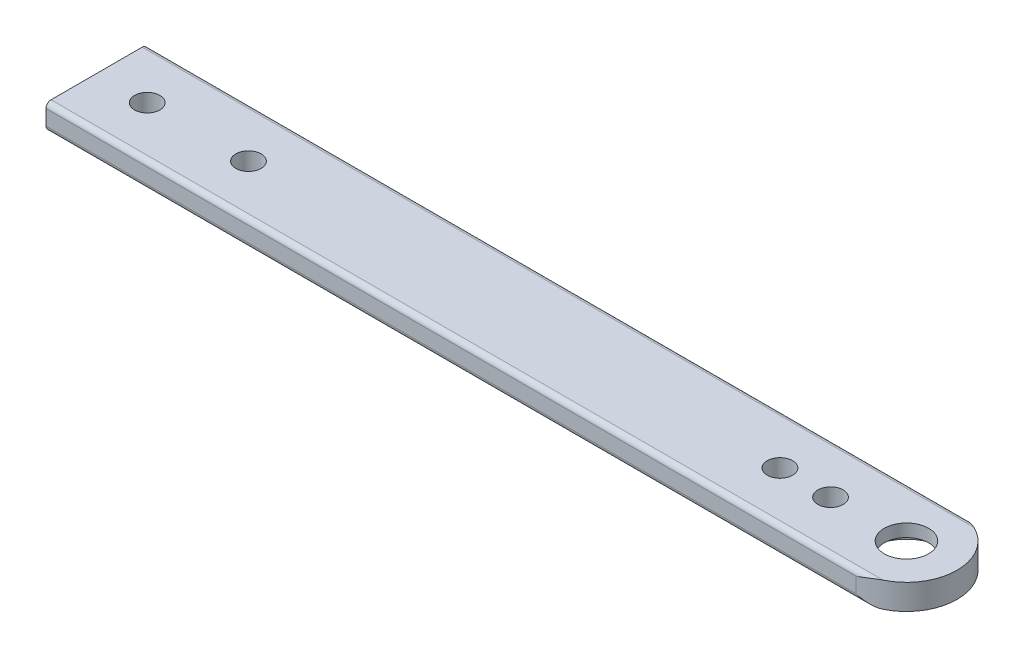
SolidWorks part; units mm, degrees
material "Plain Carbon Steel"
ref_plane "Front Plane" through (0, 0, 0) normal (0, 0, 1) x (1, 0, 0)
ref_plane "Top Plane" through (0, 0, 0) normal (0, 1, 0) x (1, 0, 0)
ref_plane "Right Plane" through (0, 0, 0) normal (1, 0, 0) x (0, 0, -1)
sketch "Sketch1" plane through (0, 0, 0) normal (0, 1, 0) x (1, 0, 0)
  line L1 (107.95, -12.7) -> (-107.95, -12.7)
  line L2 (107.95, -12.7) -> (107.95, 12.7)
  line L3 (107.95, 12.7) -> (-107.95, 12.7)
  line L4 (-107.95, -12.7) -> (-107.95, 12.7)
  line L5 (107.95, -12.7) -> (-107.95, 12.7) construction
  line L6 (107.95, 12.7) -> (-107.95, -12.7) construction
  point P0 (0, 0)
  dimension "D1" = 25.4
  dimension "D2" = 215.9
extrude "Boss-Extrude1" add sketch "Sketch1" along normal blind 6.35
fillet "Fillet1" radius 1.27 4 edges at (0, 0, -12.7) (0, 6.35, -12.7) (0, 0, 12.7) (0, 6.35, 12.7)
sketch "Sketch2" plane through (0, 6.35, 0) normal (0, 1, 0) x (1, 0, 0)
  line L0 (-107.95, 0) -> (107.95, 0) construction
  line L1 (-107.95, 11.43) -> (-107.95, -11.43) construction
  line L2 (107.95, -11.43) -> (107.95, 11.43) construction
  circle A0 centre (-95.25, 0) radius 3.175
  circle A3 centre (95.25, 0) radius 5.5563
  circle A7 centre (-69.85, 0) radius 3.175
  line M13 (107.95, 11.43) -> (-107.95, 11.43)
  line M15 (-107.95, -11.43) -> (107.95, -11.43)
  dimension "D1" = 11.1125
  dimension "D4" = 6.35
  dimension "D2" = 190.5
  dimension "D3" = 12.7
  dimension "D5" = 2
extrude "Cut-Extrude1" cut sketch "Sketch2" against normal through all contours M13 | M15 | A0 L0 | L0 A3 | A3 L0 | A0 | A7 region at (-95.25, 6.35, -1.3475) region at (95.25, 6.35, -2.3581) region at (95.25, 6.35, 2.3581)
sketch "Sketch3" plane through (0, 0, 0) normal (0, -1, 0) x (1, 0, 0)
  circle A0 centre (95.25, 0) radius 9.525
  dimension "D1" = 19.05
extrude "Cut-Extrude2" cut sketch "Sketch3" against normal blind 3.175
sketch "Sketch4" plane through (0, 0, 0) normal (0, -1, 0) x (1, 0, 0)
  line L1 (82.55, -12.7) -> (107.95, -12.7)
  line L2 (82.55, -12.7) -> (82.55, 12.7)
  line L3 (82.55, 12.7) -> (107.95, 12.7)
  line L4 (107.95, -12.7) -> (107.95, 12.7)
  line L5 (82.55, -12.7) -> (107.95, 12.7) construction
  line L6 (82.55, 12.7) -> (107.95, -12.7) construction
  circle A0 centre (95.25, 0) radius 12.7
  point P0 (95.25, 0)
  line M9 (-107.95, -11.43) -> (107.95, -11.43)
  line M10 (107.95, -11.43) -> (107.95, 11.43)
  line M11 (107.95, 11.43) -> (-107.95, 11.43)
extrude "Cut-Extrude3" cut sketch "Sketch4" against normal through all contours A0 L4 L3 M11 | A0 L4 M11 | A0 M9 M10 | A0 L1 L4 M9 region at (103.3706, 0, -12.1169) region at (105.9682, 0, -8.7575) region at (105.9682, 0, 8.7575) region at (103.3706, 0, 12.1169)
sketch "Sketch5" plane through (0, 0, 0) normal (0, -1, 0) x (1, 0, 0)
  line L0 (-107.95, 0) -> (107.95, 0) construction
  circle A0 centre (76.2, 0) radius 3.175
  circle A1 centre (63.5, 0) radius 3.175
  dimension "D1" = 6.35
  dimension "D2" = 12.7
  dimension "D3" = 19.05
extrude "Cut-Extrude4" cut sketch "Sketch5" against normal through all
